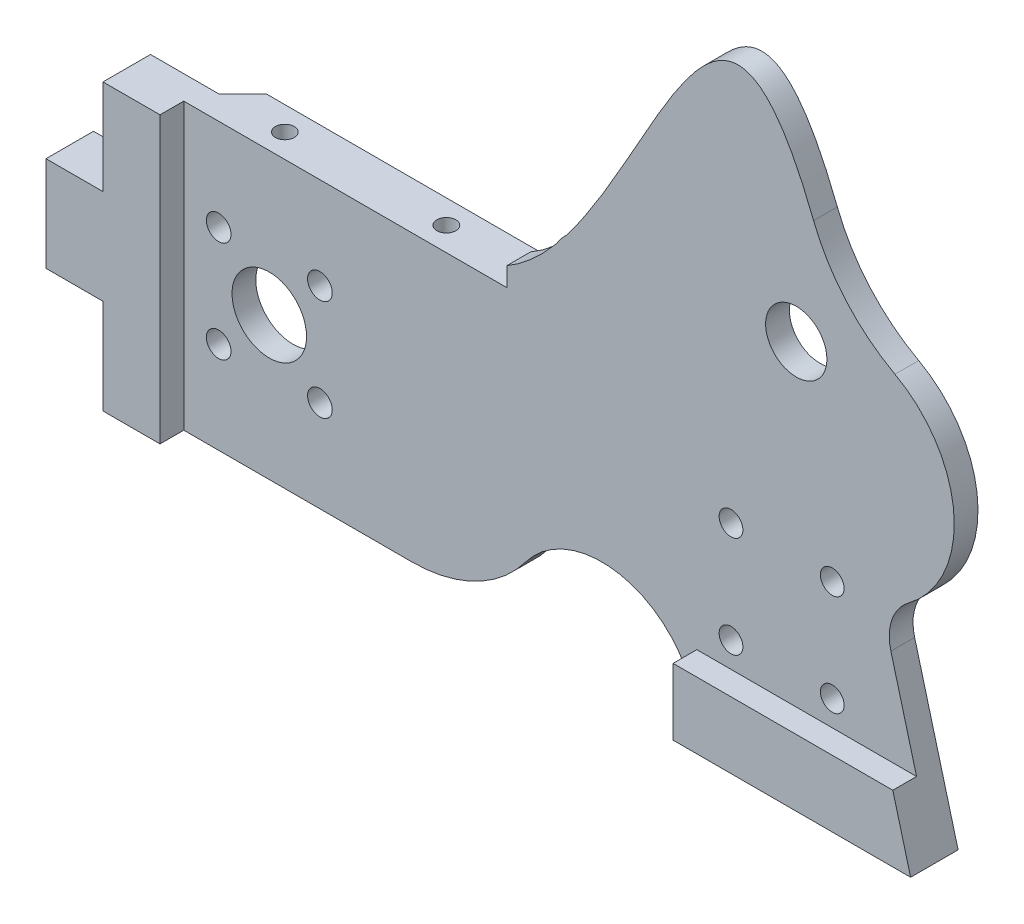
SolidWorks part; units mm, degrees
ref_plane "Front Plane" through (0, 0, 0) normal (0, 0, 1) x (1, 0, 0)
ref_plane "Top Plane" through (0, 0, 0) normal (0, 1, 0) x (1, 0, 0)
ref_plane "Right Plane" through (0, 0, 0) normal (1, 0, 0) x (0, 0, -1)
sketch "Sketch1" plane through (0, 0, 0) normal (0, 0, 1) x (1, 0, 0)
  line L0 (0, 0) -> (107.95, 0)
  line L3 (0, 38.1) -> (0, 25.4)
  line L4 (95.3675, 55.88) -> (0, 38.1)
  line L5 (0, 19.05) -> (100.2273, 19.05) construction
  line L6 (19.05, 19.05) -> (19.05, 28.62) construction
  line L7 (19.05, 19.05) -> (25.817, 25.817) construction
  line L8 (107.95, 0) -> (100.9363, 26.1756)
  line L10 (0, 12.7) -> (0, 0)
  line L11 (0, 25.4) -> (-7.62, 25.4)
  line L13 (0, 12.7) -> (-7.62, 12.7)
  line L14 (-7.62, 25.4) -> (-7.62, 12.7)
  line L15 (100.9363, 26.1756) -> (100.8688, 26.4276)
  arc A0 (100.8688, 26.4276) -> (95.3675, 55.88) centre (95.3675, 40.64) ccw
  circle A1 centre (95.3675, 40.64) radius 4.0957 construction
  circle A2 centre (19.05, 19.05) radius 9.57 construction
  circle A3 centre (25.817, 25.817) radius 1.651
  circle A4 centre (25.817, 12.283) radius 1.651
  circle A5 centre (12.283, 12.283) radius 1.651
  circle A6 centre (12.283, 25.817) radius 1.651
  point P26 (19.05, 19.05)
  dimension "D1" = 8.1915
  dimension "D5" = 15.24
  dimension "D4" = 19.14
  dimension "D7" = 3.302
  dimension "D11" = 97.0107
  dimension "D2" = 38.1
  dimension "D3" = 40.64
  dimension "D6" = 107.95
  dimension "D8" = 45
  dimension "D9" = 4
  dimension "D10" = 19.05
  dimension "D12" = 75
  dimension "D14" = 12.7
  dimension "D15" = 12.7
  dimension "D16" = 7.62
extrude "Boss-Extrude1" add sketch "Sketch1" along normal blind 3.175
sketch "Sketch2" plane through (0, 0, 3.175) normal (0, 0, 1) x (1, 0, 0)
  circle A0 centre (95.3675, 40.64) radius 38.1 construction
sketch "Sketch6" plane through (0, 0, 3.175) normal (0, 0, 1) x (1, 0, 0)
  line L0 (0, 0) -> (107.95, 0) construction
  line L1 (50.8, 0) -> (76.2, 0)
  arc A0 (76.2, 0) -> (50.8, 0) centre (63.5, 0) ccw
  dimension "D1" = 25.4
  dimension "D2" = 31.75
extrude "Cut-Extrude2" cut sketch "Sketch6" against normal blind 6.35
sketch "Sketch7" plane through (0, 0, 3.175) normal (0, 0, 1) x (1, 0, 0)
  line L0 (12.283, 25.817) -> (25.817, 12.283) construction
  line L1 (12.283, 12.283) -> (25.817, 25.817) construction
  line L2 (12.283, 25.817) -> (78.4839, 25.817) construction
  line L3 (11.7326, 12.283) -> (12.283, 12.283) construction
  circle A0 centre (19.05, 19.05) radius 4.9784
  circle A4 centre (80.7666, 12.283) radius 1.5875
  circle A5 centre (94.2997, 12.283) radius 1.5875
  circle A6 centre (80.7666, 25.817) radius 1.5875
  circle A7 centre (94.2997, 25.817) radius 1.5875
  dimension "D1" = 9.9568
  dimension "D2" = 3.175
  dimension "D3" = 13.5331
extrude "Cut-Extrude3" cut sketch "Sketch7" against normal through all
fillet "Fillet1" radius 6.35 1 edges at (100.8688, 26.4276, 1.5875)
sketch "Sketch8" plane through (0, 0, 3.175) normal (0, 0, 1) x (1, 0, 0)
  line L1 (0, 38.1) -> (50.8, 38.1)
  line L2 (0, 38.1) -> (0, 50.8)
  line L3 (0, 50.8) -> (50.8, 50.8)
  line L4 (50.8, 38.1) -> (50.8, 50.8)
  dimension "D1" = 50.8
  dimension "D2" = 12.7
extrude "Cut-Extrude4" cut sketch "Sketch8" against normal blind 50.8
sketch "Sketch9" plane through (0, 0, 3.175) normal (0, 0, 1) x (1, 0, 0)
  line L3 (50.8, 40.64) -> (57.15, 40.64)
  line L5 (57.15, 40.64) -> (50.8, 40.64)
  line L6 (57.15, 40.64) -> (57.15, 50.8)
  line L7 (57.15, 50.8) -> (50.8, 50.8)
  line L8 (50.8, 40.64) -> (50.8, 50.8)
  line L9 (0, 38.1) -> (50.8, 38.1) construction
  line M8 (50.8, 47.571) -> (50.8, 38.1)
  line M21 (95.3675, 55.88) -> (50.8, 47.571)
  dimension "D1" = 10.16
  dimension "D2" = 2.54
  dimension "D3" = 6.35
extrude "Cut-Extrude5" cut sketch "Sketch9" against normal blind 19.304 contours L3 L6 M21 M8
fillet "Fillet6" radius 6.35 1 edges at (57.15, 40.64, 1.5875)
fillet "Fillet7" radius 6.35 1 edges at (57.15, 48.7549, 1.5875)
fillet "Fillet8" radius 19.05 1 edges at (50.8, 0, 1.5875)
sketch "Sketch12" plane through (0, 0, 3.175) normal (0, 0, 1) x (1, 0, 0)
  line L0 (107.95, 0) -> (146.812, 0) construction
  line L1 (8.0257, 45.4128) -> (80.6683, 75.7903) construction
  line L2 (95.3675, 40.64) -> (80.6683, 75.7903) construction
  line L3 (80.6683, 75.7903) -> (79.4434, 78.7195) construction
  line L4 (50.8, 40.64) -> (85.0271, 40.64)
  line L5 (85.0271, 40.64) -> (95.3675, 55.88)
  arc A0 (61.8128, 49.6242) -> (56.8883, 45.1859) centre (62.9766, 43.3817) ccw construction
  circle A1 centre (19.05, 19.05) radius 28.575 construction
  circle A2 centre (95.3675, 40.64) radius 38.1 construction
  circle A3 centre (80.6683, 75.7903) radius 3.175 construction
  spline S0 degree 3 poles (50.8, 40.64) (70.7778, 52.1788) (78.5943, 111.5434) (95.3675, 55.88) knots 0 0 0 0 1 1 1 1
  dimension "D2" = 6.35
  dimension "D1" = 38.862
extrude "Boss-Extrude2" add sketch "Sketch12" against normal blind 3.175
fillet "Fillet9" radius 24.13 1 edges at (95.3675, 55.88, 1.5875)
sketch "Sketch13" plane through (0, 0, 0) normal (0, 0, -1) x (-1, 0, 0)
  line L1 (-50.8, 38.1) -> (-9.1321, 38.1)
  line L2 (-50.8, 38.1) -> (-50.8, 28.6404)
  line L3 (-50.8, 28.6404) -> (-9.1321, 28.6404)
  line L6 (-9.1321, 8.4682) -> (-38.1, 8.4682)
  line L7 (-9.1321, 8.4682) -> (-9.1321, 0)
  line L8 (-9.1321, 0) -> (-38.1, 0)
  line L9 (-38.1, 8.4682) -> (-38.1, 0)
  line L10 (-9.1321, 38.1) -> (-9.1321, 28.6404)
extrude "Boss-Extrude3" add sketch "Sketch13" along normal blind 3.175
sketch "Sketch18" plane through (0, 0, 3.175) normal (0, 0, 1) x (1, 0, 0)
  line L0 (0, 0) -> (7.62, 0)
  line L1 (0, 0) -> (38.1, 0) construction
  line L2 (7.62, 0) -> (7.62, 38.1)
  line L3 (0, 38.1) -> (50.8, 38.1) construction
  line L4 (7.62, 38.1) -> (0, 38.1)
  line L5 (0, 38.1) -> (0, 25.4)
  line L6 (0, 25.4) -> (-7.62, 25.4)
  line L7 (-7.62, 25.4) -> (-7.62, 12.7)
  line L8 (-7.62, 12.7) -> (0, 12.7)
  line L9 (0, 12.7) -> (0, 0)
  dimension "D1" = 7.62
extrude "Boss-Extrude4" add sketch "Sketch18" along normal blind 3.175
sketch "Sketch19" plane through (0, 38.1, 0) normal (0, 1, 0) x (1, 0, 0)
  line L0 (9.1321, 0) -> (12.3071, 3.175)
  line L1 (9.1321, 3.175) -> (50.8, 3.175) construction
  line L2 (9.1321, 3.175) -> (9.1321, 0) construction
  line L3 (12.3071, 3.175) -> (9.1321, 3.175)
  line L4 (9.1321, 3.175) -> (9.1321, 0)
  dimension "D1" = 45
extrude "Cut-Extrude9" cut sketch "Sketch19" against normal through all
extrude "Cut-Extrude10" cut sketch "Sketch20" against normal blind 3.81
sketch "Sketch20" plane through (18.3095, 38.1, -53.6674) normal (0, 1, 0) x (0.9999, 0, -0.0134)
  circle A0 centre (-1.0738, -53.6578) radius 1.27
  circle A1 centre (20.5143, -53.9464) radius 1.27
  circle A2 centre (-1.6662, -97.9769) radius 1.27
  circle A3 centre (19.9218, -98.2655) radius 1.27
extrude "Cut-Extrude11" cut sketch "Sketch21" against normal blind 6.35
sketch "Sketch21" plane through (0, -69.8383, -53.6674) normal (-1, 0, 0) x (0, 0.0319, 0.9995)
  circle A0 centre (98.0061, 98.5137) radius 1.27
  circle A1 centre (97.1963, 73.1266) radius 1.27
  circle A2 centre (59.2426, 74.3373) radius 1.27
  circle A3 centre (60.0524, 99.7243) radius 1.27
extrude "Cut-Extrude12" cut sketch "Sketch22" against normal blind 6.35
sketch "Sketch22" plane through (18.3095, 0, -53.6674) normal (0, -1, 0) x (0.9999, 0, -0.0134)
  circle A1 centre (-5.686, 53.4819) radius 1.27
  circle A2 centre (13.3623, 53.7365) radius 1.27
  circle A3 centre (67.9469, 56.8794) radius 1.27
  circle A4 centre (79.3759, 57.0322) radius 1.27
  circle A5 centre (78.8449, 96.7542) radius 1.27
  circle A6 centre (67.4159, 96.6014) radius 1.27
  circle A7 centre (12.7668, 98.2841) radius 1.27
  circle A8 centre (-6.2815, 98.0295) radius 1.27
sketch "Sketch23" plane through (0, 0, 3.175) normal (0, 0, 1) x (1, 0, 0)
  line L0 (76.2, 0) -> (76.2, 8.89)
  line L1 (76.2, 8.89) -> (105.5679, 8.89)
  line L2 (107.95, 0) -> (102.1388, 21.6878) construction
  line L3 (105.5679, 8.89) -> (107.95, 0)
  line L4 (107.95, 0) -> (76.2, 0)
  dimension "D1" = 8.89
extrude "Boss-Extrude5" add sketch "Sketch23" along normal blind 3.175
extrude "Cut-Extrude13" cut sketch "Sketch24" against normal up to surface (3.175 mm away) up to face at (24.0284, 19.05, 0)
sketch "Sketch24" plane through (18.3095, -69.8383, 3.175) normal (0, 0, 1) x (0.9998, 0.0192, 0)
  circle A0 centre (73.4967, 119.6334) radius 4.0958
